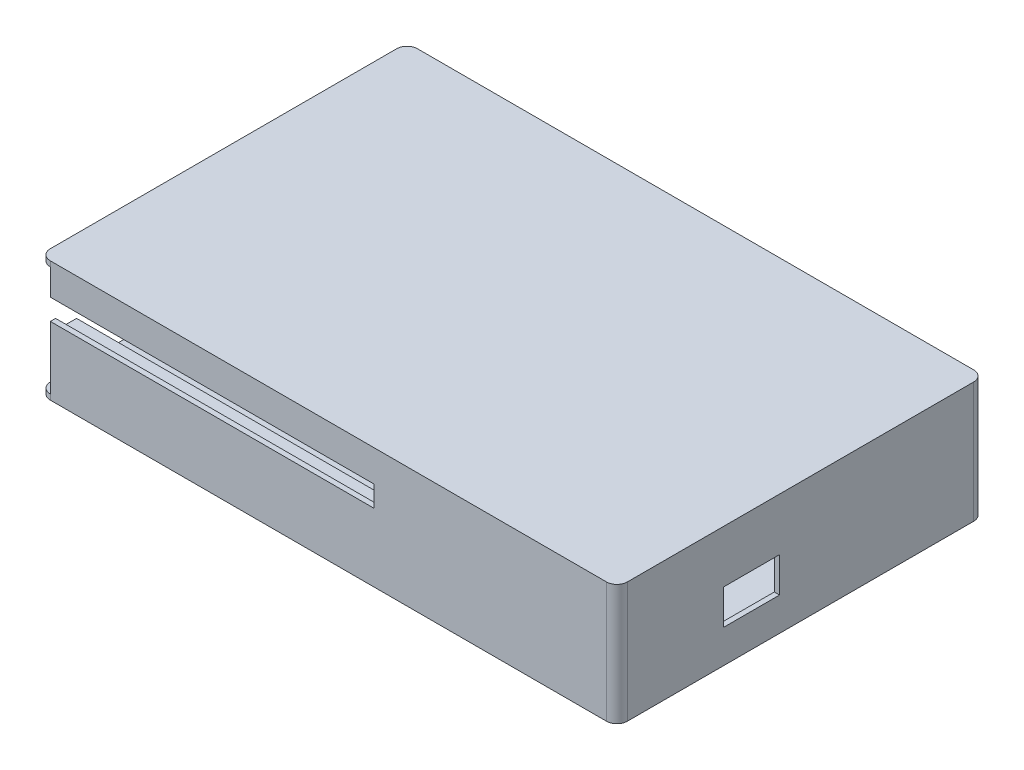
SolidWorks part; units mm, degrees
ref_plane "Front Plane" through (0, 0, 0) normal (0, 0, 1) x (1, 0, 0)
ref_plane "Top Plane" through (0, 0, 0) normal (0, 1, 0) x (1, 0, 0)
ref_plane "Right Plane" through (0, 0, 0) normal (1, 0, 0) x (0, 0, -1)
sketch "Sketch1" plane through (0, 0, 0) normal (0, 1, 0) x (1, 0, 0)
  line L0 (0.75, 51.75) -> (0.75, -0.75)
  line L1 (0.75, 0) -> (80.25, 0)
  line L2 (0, 0.75) -> (0, 50.25)
  line L3 (0.75, 51) -> (80.25, 51)
  line L4 (81, 0.75) -> (81, 50.25)
  line L5 (0.75, 51.75) -> (80.25, 51.75)
  line L6 (-0.75, 50.25) -> (-0.75, 0.75)
  line L7 (0.75, -0.75) -> (80.25, -0.75)
  line L8 (81.75, 50.25) -> (81.75, 0.75)
  line L13 (0, 49.5) -> (81, 49.5)
  line L14 (81, 1.5) -> (0, 1.5)
  line L16 (-0.75, 37.5) -> (0, 37.5)
  line L17 (-0.75, 21.5) -> (0, 21.5)
  line L18 (81, 14.5) -> (81.75, 14.5)
  line L19 (81, 22.5) -> (81.75, 22.5)
  line L20 (47, 51.75) -> (47, 51)
  line L21 (47, 0) -> (47, -0.75)
  arc A0 (0.75, 51) -> (0, 50.25) centre (0.75, 50.25) ccw
  arc A1 (0, 0.75) -> (0.75, 0) centre (0.75, 0.75) ccw
  arc A2 (80.25, 0) -> (81, 0.75) centre (80.25, 0.75) ccw
  arc A3 (80.25, 51) -> (81, 50.25) centre (80.25, 50.25) cw
  arc A4 (-0.75, 0.75) -> (0.75, -0.75) centre (0.75, 0.75) ccw
  arc A5 (80.25, -0.75) -> (81.75, 0.75) centre (80.25, 0.75) ccw
  arc A6 (81.75, 50.25) -> (80.25, 51.75) centre (80.25, 50.25) ccw
  arc A7 (0.75, 51.75) -> (-0.75, 50.25) centre (0.75, 50.25) ccw
  point P11 (0, 51)
  point P14 (0, 0)
  point P19 (81, 51)
  dimension "D7" = 0.75
  dimension "D8" = 1.5
  dimension "D1" = 51
  dimension "D2" = 81
  dimension "D3" = 0.75
  dimension "D4" = 0.75
  dimension "D5" = 0.75
  dimension "D6" = 0.75
  dimension "D9" = 1.5
  dimension "D10" = 1.5
  dimension "D11" = 13.5
  dimension "D12" = 16
  dimension "D13" = 14.5
  dimension "D14" = 8
  dimension "D15" = 47
extrude "Boss-Extrude1" add sketch "Sketch1" along normal blind 0.75 contours L6 A4 L7 A5 L8 A6 L5 A7
extrude "Boss-Extrude2" add sketch "Sketch1<3>" along normal blind 3.75 contours A3 L3 L13 L4 | L1 A2 L4 L14 region at (40.8349, 0, -50.2494) region at (40.8349, 0, -0.7506)
sketch "Sketch1<3>" plane through (0, 0, 0) normal (0, 1, 0) x (1, 0, 0) same geometry as "Sketch1"
extrude "Boss-Extrude3" add sketch "Sketch1<4>" along normal blind 9.75 contours L7 A5 L8 L18 L4 A2 L1 L21 | L8 A6 L5 L20 L3 A3 L4 L19 | L21 L1 L0 L7 | L20 L5 L0 L3 region at (23.875, 0, -51.375) region at (63.625, 0, -51.2958) region at (23.875, 0, 0.375) region at (81.3795, 0, -8)
sketch "Sketch1<4>" plane through (0, 0, 0) normal (0, 1, 0) x (1, 0, 0) same geometry as "Sketch1"
extrude "Boss-Extrude4" add sketch "Sketch1<5>" along normal blind 4.75 contours L19 L4 L18 L8 region at (81.375, 0, -18.5)
sketch "Sketch1<5>" plane through (0, 0, 0) normal (0, 1, 0) x (1, 0, 0) same geometry as "Sketch1"
extrude "Boss-Extrude5" add sketch "Sketch1<8>" along normal blind 7 from offset 9.75 contours L7 A5 L8 L18 L4 A2 L1 L21 | L19 L4 L18 L8 | L8 A6 L5 L20 L3 A3 L4 L19 region at (63.625, 0, -51.2958) region at (81.3795, 0, -8) region at (81.375, 0, -18.5)
sketch "Sketch1<8>" plane through (0, 0, 0) normal (0, 1, 0) x (1, 0, 0) same geometry as "Sketch1"
extrude "Boss-Extrude6" add sketch "Sketch1<9>" along normal blind 3 from offset 5.25 contours A3 L3 L0 L13 L4 | L1 A2 L4 L14 L0 region at (40.8349, 0, -50.2494) region at (40.8349, 0, -0.7506)
sketch "Sketch1<9>" plane through (0, 0, 0) normal (0, 1, 0) x (1, 0, 0) same geometry as "Sketch1"
extrude "Boss-Extrude7" add sketch "Sketch1<11>" along normal blind 4 from offset 12.75 contours L21 L1 L0 L7 | L20 L5 L0 L3 region at (23.875, 0, -51.375) region at (23.875, 0, 0.375)
sketch "Sketch1<11>" plane through (0, 0, 0) normal (0, 1, 0) x (1, 0, 0) same geometry as "Sketch1"
extrude "Boss-Extrude9" add sketch "Sketch1<12>" along normal blind 0.75 from offset 16.5 contours L14 L4 L13 L0 | A3 L3 L0 L13 L4 | L20 L5 L0 L3 | L1 A2 L4 L14 L0 | L21 L1 L0 L7 | L7 A5 L8 L18 L4 A2 L1 L21 | L19 L4 L18 L8 | L0 A7 L6 L16 L2 A0 | L0 A0 L2 L13 | L14 L0 L13 L2 | L6 L17 L2 L16 | L6 A4 L0 A1 L2 L17 | L2 A1 L0 L14 | L8 A6 L5 L20 L3 A3 L4 L19 region at (23.875, 0, -51.375) region at (-0.3285, 0, -44.7414) region at (40.8349, 0, -50.2494) region at (0.3999, 0, -50.18) region at (63.625, 0, -51.2958) region at (40.875, 0, -25.5) region at (0.375, 0, -25.5) region at (-0.375, 0, -29.5) region at (40.8349, 0, -0.7506) region at (0.3999, 0, -0.82) region at (-0.345, 0, -10.2525) region at (23.875, 0, 0.375) region at (81.3795, 0, -8) region at (81.375, 0, -18.5)
sketch "Sketch1<12>" plane through (0, 0, 0) normal (0, 1, 0) x (1, 0, 0) same geometry as "Sketch1"
sketch "Sketch3" plane through (0, 0, -49.5) normal (0, 0, 1) x (1, 0, 0)
  line L1 (81, 8.25) -> (0.75, 8.25)
  line L2 (81, 8.25) -> (81, 5.25)
  line L3 (81, 5.25) -> (0.75, 5.25)
  line L4 (0.75, 8.25) -> (0.75, 5.25)
extrude "Boss-Extrude10" add sketch "Sketch3" along normal blind 1.5
sketch "Sketch4" plane through (0.75, 0, 0) normal (-1, 0, 0) x (0, 0, 1)
  line L0 (-51, 8.25) -> (-48, 5.25) construction
  line L1 (-48, 8.25) -> (-51, 5.25) construction
  circle A0 centre (-49.5, 6.75) radius 0.6
sketch "Sketch6" plane through (0, 0, -1.5) normal (0, 0, -1) x (-1, 0, 0)
  line L1 (-81, 5.25) -> (-0.75, 5.25)
  line L2 (-81, 5.25) -> (-81, 8.25)
  line L3 (-81, 8.25) -> (-0.75, 8.25)
  line L4 (-0.75, 5.25) -> (-0.75, 8.25)
extrude "Boss-Extrude11" add sketch "Sketch6" along normal blind 1.5
sketch "Sketch7" plane through (0.75, 0, 0) normal (-1, 0, 0) x (0, 0, 1)
  line L0 (0, 5.25) -> (-3, 8.25) construction
  line L1 (0, 8.25) -> (-3, 5.25) construction
  circle A0 centre (-1.5, 6.75) radius 0.6
extrude "Cut-Extrude1" cut sketch "Sketch4" against normal blind 79 contours A0
extrude "Cut-Extrude2" cut sketch "Sketch7" against normal blind 79
